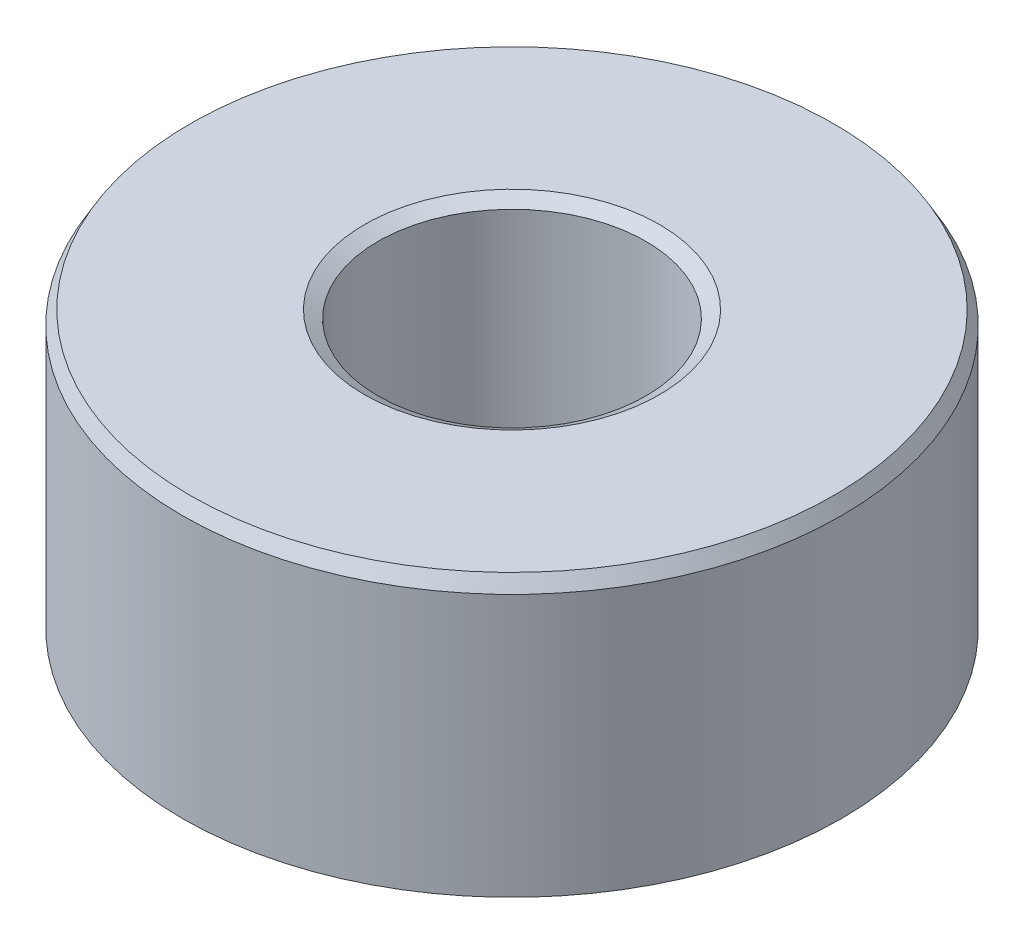
SolidWorks part; units mm, degrees
ref_plane "Front Plane" through (0, 0, 0) normal (0, 0, 1) x (1, 0, 0)
ref_plane "Top Plane" through (0, 0, 0) normal (0, 1, 0) x (1, 0, 0)
ref_plane "Right Plane" through (0, 0, 0) normal (1, 0, 0) x (0, 0, -1)
sketch "Sketch1" plane through (0, 0, 0) normal (0, 1, 0) x (1, 0, 0)
  circle A0 centre (0, 0) radius 60
  dimension "SLEEVE_OD" = 120
extrude "Boss-Extrude1" add sketch "Sketch1" along normal blind 51.6246
sketch "Sketch2" plane through (0, 0, 0) normal (0, 1, 0) x (1, 0, 0)
  circle A0 centre (0, 0) radius 24.3781
  dimension "BORE_D" = 48.7562
extrude "Cut-Extrude1" cut sketch "Sketch2" along normal through all
chamfer "Chamfer1" distance 2.4632 angle 30 4 edges at (0, 51.6246, 24.3781) (0, 0, 24.3781) (0, 0, 60) (0, 51.6246, 60) first distance on face at (0, 51.6246, 24.3781) first distance on face at (0, 0, 24.3781) first distance on face at (0, 51.6246, 60)
